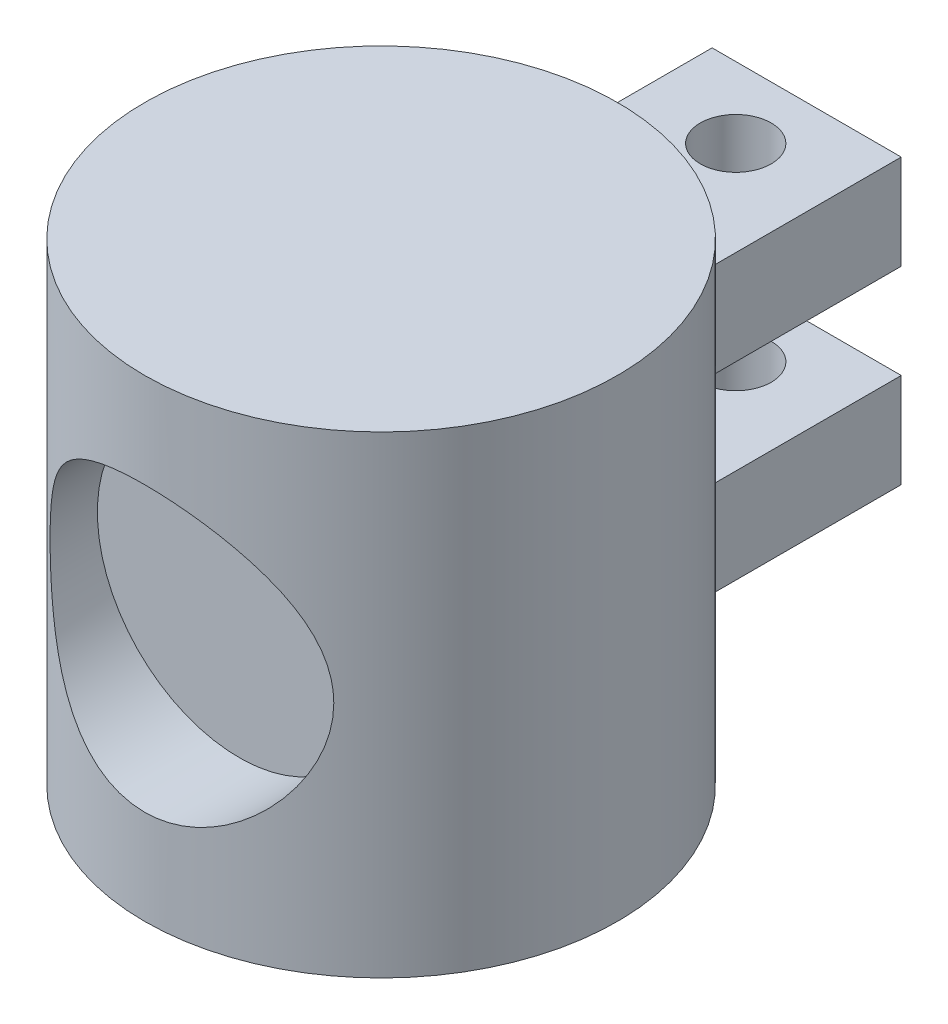
SolidWorks part; units mm, degrees
ref_plane "Front Plane" through (0, 0, 0) normal (0, 0, 1) x (1, 0, 0)
ref_plane "Top Plane" through (0, 0, 0) normal (0, 1, 0) x (1, 0, 0)
ref_plane "Right Plane" through (0, 0, 0) normal (1, 0, 0) x (0, 0, -1)
sketch "Sketch1" plane through (0, 0, 0) normal (0, 1, 0) x (1, 0, 0)
  circle A0 centre (0, 0) radius 50
  dimension "D1" = 100
extrude "Boss-Extrude1" add sketch "Sketch1" along normal blind 100
ref_plane "Plane1" through (0, 0, 50) normal (0, 0, 1) x (1, 0, 0)
sketch "Sketch2" plane through (0, 0, 50) normal (0, 0, 1) x (1, 0, 0)
  circle A0 centre (0, 50) radius 30
  dimension "D1" = 60
extrude "Cut-Extrude1" cut sketch "Sketch2" against normal blind 20
ref_plane "Plane6" through (0, 0, -90) normal (0, 0, 1) x (1, 0, 0)
sketch "Sketch9" plane through (0, 0, -90) normal (0, 0, 1) x (1, 0, 0)
  line L1 (20, 80) -> (-20, 80)
  line L2 (20, 80) -> (20, 60)
  line L3 (20, 60) -> (-20, 60)
  line L4 (-20, 80) -> (-20, 60)
  line L5 (20, 80) -> (-20, 60) construction
  line L6 (20, 60) -> (-20, 80) construction
  line L7 (20, 20) -> (-20, 20)
  line L8 (20, 20) -> (20, 40)
  line L9 (20, 40) -> (-20, 40)
  line L10 (-20, 20) -> (-20, 40)
  line L11 (20, 20) -> (-20, 40) construction
  line L12 (20, 40) -> (-20, 20) construction
  point P0 (0, 70)
  point P5 (0, 30)
  dimension "D1" = 40
  dimension "D6" = 40
  dimension "D7" = 0
extrude "Boss-Extrude4" add sketch "Sketch9" along normal up to surface (44.1742 mm away) up to face at (-29.9999, 49.9351, 40.0001)
sketch "Sketch10" plane through (0, 80, 0) normal (0, 1, 0) x (1, 0, 0)
  line L0 (-55, 90) -> (55, 90) construction
  circle A0 centre (0, 75) radius 7.5
  dimension "D2" = 15
  dimension "D1" = 15
extrude "Cut-Extrude4" cut sketch "Sketch10" against normal blind 100
